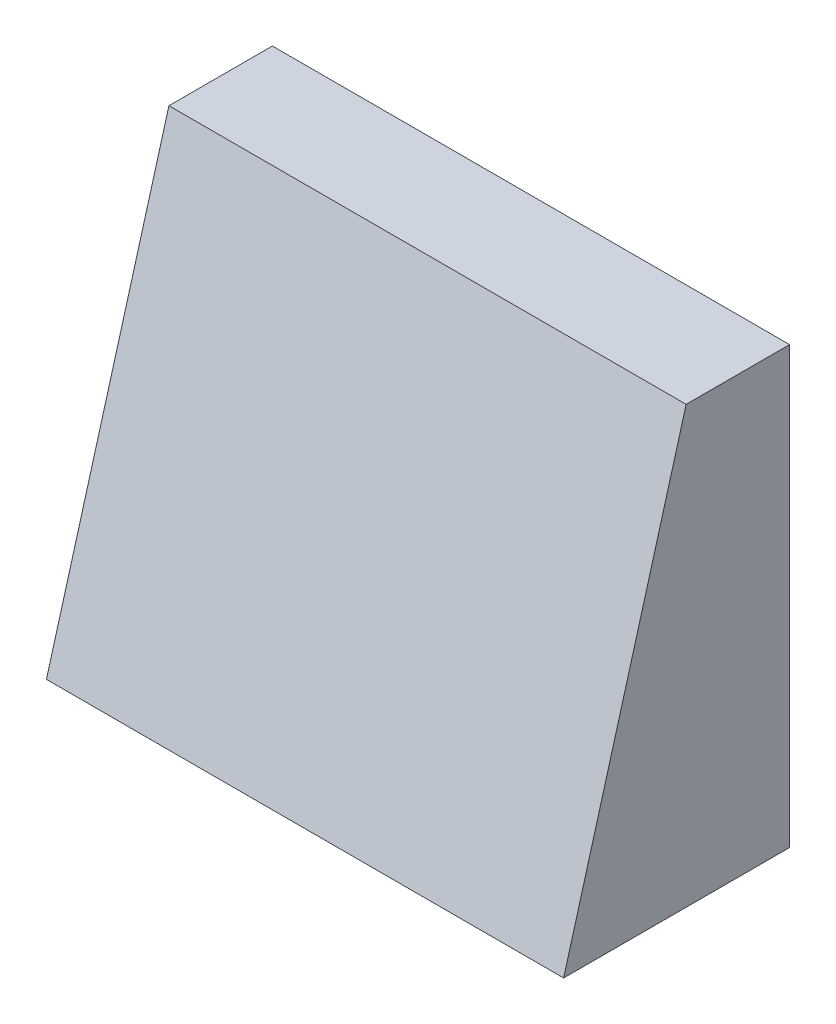
SolidWorks part; units mm, degrees
ref_plane "Front Plane" through (0, 0, 0) normal (0, 0, 1) x (1, 0, 0)
ref_plane "Top Plane" through (0, 0, 0) normal (0, 1, 0) x (1, 0, 0)
ref_plane "Right Plane" through (0, 0, 0) normal (1, 0, 0) x (0, 0, -1)
sketch "Sloped Cover Outer Side Profile" plane through (0, 0, 0) normal (1, 0, 0) x (0, 0, -1)
  line L0 (-22, 40) -> (-22, 200)
  line L1 (-22, 200) -> (-60, 200)
  line L2 (-60, 200) -> (-105, 40)
  line L3 (-105, 40) -> (-22, 40)
extrude "Sloped Cover Blank" add sketch "Sloped Cover Outer Side Profile" along normal blind 95 and the other way blind 95 separate body
sketch "Open Bottom Cover Cavity Profile" plane through (0, 0, 0) normal (1, 0, 0) x (0, 0, -1)
  line L0 (-18, 38) -> (-18, 193)
  line L1 (-18, 193) -> (-56, 193)
  line L2 (-56, 193) -> (-101, 38)
  line L3 (-101, 38) -> (-18, 38)
extrude "Open Bottom and Front Cover Cavity" cut sketch "Open Bottom Cover Cavity Profile" against normal blind 88 and the other way blind 88
sketch "Front Gasket Compression Rail Profile" plane through (0, 0, 0) normal (1, 0, 0) x (0, 0, -1)
  line L0 (-22, 45) -> (-22, 52)
  line L1 (-22, 40) -> (-22, 200) construction
  line L2 (-22, 52) -> (-25, 52)
  line L3 (-25, 52) -> (-25, 45)
  line L4 (-25, 45) -> (-22, 45)
extrude "Front Gasket Compression Rail" add sketch "Front Gasket Compression Rail Profile" along normal blind 95 and the other way blind 95
